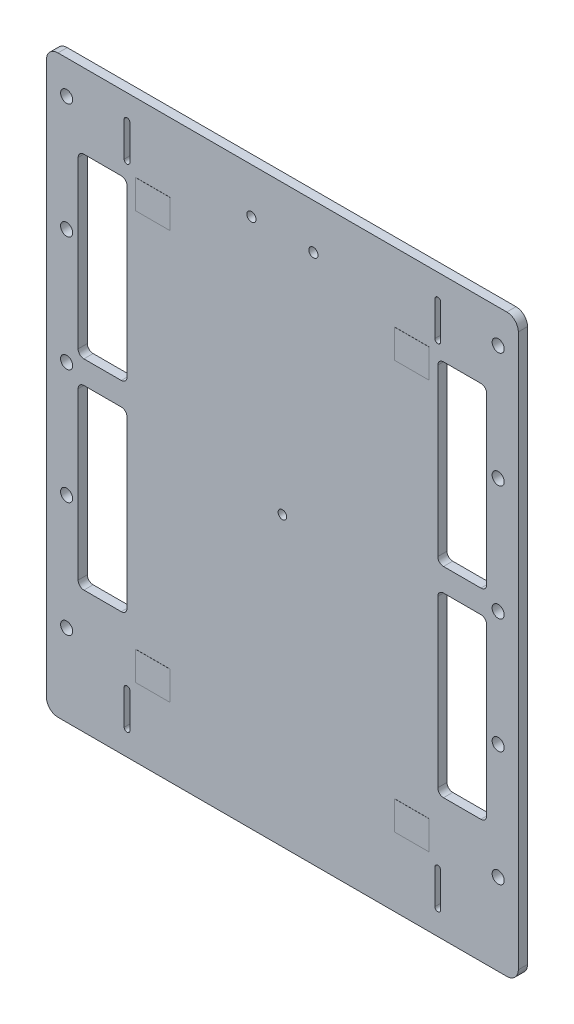
SolidWorks part; units mm, degrees
material "Oshpark board"
ref_plane "Front Plane" through (0, 0, 0) normal (0, 0, 1) x (1, 0, 0)
ref_plane "Top Plane" through (0, 0, 0) normal (0, 1, 0) x (1, 0, 0)
ref_plane "Right Plane" through (0, 0, 0) normal (1, 0, 0) x (0, 0, -1)
sketch "Sketch1" plane through (0, 0, 0) normal (0, 0, 1) x (1, 0, 0)
  line L1 (-39, -50) -> (39, -50)
  line L2 (-41, -48) -> (-41, 48)
  line L3 (-39, 50) -> (39, 50)
  line L4 (41, -48) -> (41, 48)
  line L5 (-41, -50) -> (41, 50) construction
  line L6 (-41, 50) -> (41, -50) construction
  arc A0 (-39, -50) -> (-41, -48) centre (-39, -48) cw
  arc A1 (39, -50) -> (41, -48) centre (39, -48) ccw
  arc A2 (39, 50) -> (41, 48) centre (39, 48) cw
  arc A3 (-41, 48) -> (-39, 50) centre (-39, 48) cw
  point P0 (0, 0)
  dimension "D3" = 2
  dimension "D1" = 100
  dimension "D2" = 82
extrude "Boss-Extrude1" add sketch "Sketch1" along normal blind 1.6
sketch "Sketch2" plane through (0, 0, 1.6) normal (0, 0, 1) x (1, 0, 0)
  line L0 (39, 50) -> (-39, 50) construction
  line L1 (-41, 48) -> (-41, -48) construction
  line L3 (-37.5, 44.2) -> (-37.5, 4.2) construction
  circle A0 centre (0, 0) radius 0.75
  circle A1 centre (-37.5, 44.2) radius 1.05
  circle A2 centre (37.5, 44.2) radius 1.05
  circle A3 centre (37.5, 4.2) radius 1.05
  circle A4 centre (37.5, -35.8) radius 1.05
  circle A5 centre (-37.5, 4.2) radius 1.05
  circle A6 centre (-37.5, -35.8) radius 1.05
  circle A7 centre (-5.38, 42.15) radius 0.8
  circle A8 centre (5.39, 42.15) radius 0.8
  dimension "D1" = 1.5
  dimension "D2" = 2.1
  dimension "D9" = 10.77
  dimension "D7" = 1.6
  dimension "D11" = 7.85
  dimension "D12" = 35.62
  dimension "D3" = 5.8
  dimension "D4" = 3.5
  dimension "D8" = 40
  dimension "D10" = 37.5
  dimension "D5" = 2
  dimension "D6" = 3
extrude "Cut-Extrude1" cut sketch "Sketch2" against normal through all
sketch "Sketch3" plane through (0, 0, 1.6) normal (0, 0, 1) x (1, 0, 0)
  line L0 (39, 50) -> (-39, 50) construction
  line L1 (-34.5, 37) -> (-28, 37)
  line L2 (-35.5, 36) -> (-35.5, 7.2)
  line L3 (-34.5, 6.2) -> (-28, 6.2)
  line L4 (-27, 36) -> (-27, 7.2)
  line L5 (-41, 48) -> (-41, -48) construction
  line L6 (28, 37) -> (34.5, 37)
  line L7 (27, 36) -> (27, 7.2)
  line L8 (35.5, 36) -> (35.5, 7.2)
  line L9 (28, 6.2) -> (34.5, 6.2)
  line L10 (28, 2.2) -> (34.5, 2.2)
  line L11 (27, 1.2) -> (27, -27.6)
  line L12 (35.5, 1.2) -> (35.5, -27.6)
  line L13 (28, -28.6) -> (34.5, -28.6)
  line L14 (-34.5, 2.2) -> (-28, 2.2)
  line L15 (-35.5, 1.2) -> (-35.5, -27.6)
  line L16 (-27, 1.2) -> (-27, -27.6)
  line L17 (-34.5, -28.6) -> (-28, -28.6)
  line L18 (-34.5, 37) -> (28, 37) construction
  line L19 (-39, -50) -> (39, -50) construction
  arc A0 (-35.5, 7.2) -> (-34.5, 6.2) centre (-34.5, 7.2) ccw
  arc A1 (-28, 6.2) -> (-27, 7.2) centre (-28, 7.2) ccw
  arc A2 (-28, 37) -> (-27, 36) centre (-28, 36) cw
  arc A3 (-34.5, 37) -> (-35.5, 36) centre (-34.5, 36) ccw
  arc A4 (28, 37) -> (27, 36) centre (28, 36) ccw
  arc A5 (34.5, 37) -> (35.5, 36) centre (34.5, 36) cw
  arc A6 (27, 7.2) -> (28, 6.2) centre (28, 7.2) ccw
  arc A7 (34.5, 6.2) -> (35.5, 7.2) centre (34.5, 7.2) ccw
  arc A8 (28, 2.2) -> (27, 1.2) centre (28, 1.2) ccw
  arc A9 (34.5, 2.2) -> (35.5, 1.2) centre (34.5, 1.2) cw
  arc A10 (27, -27.6) -> (28, -28.6) centre (28, -27.6) ccw
  arc A11 (34.5, -28.6) -> (35.5, -27.6) centre (34.5, -27.6) ccw
  arc A12 (-34.5, 2.2) -> (-35.5, 1.2) centre (-34.5, 1.2) ccw
  arc A13 (-28, 2.2) -> (-27, 1.2) centre (-28, 1.2) cw
  arc A14 (-35.5, -27.6) -> (-34.5, -28.6) centre (-34.5, -27.6) ccw
  arc A15 (-28, -28.6) -> (-27, -27.6) centre (-28, -27.6) ccw
  point P12 (-27, 6.2)
  point P15 (-27, 37)
  point P18 (-35.5, 37)
  dimension "D5" = 1
  dimension "D10" = 27
  dimension "D1" = 8.5
  dimension "D2" = 30.8
  dimension "D3" = 13
  dimension "D4" = 5.5
  dimension "D8" = 62.5
  dimension "D9" = 4
  dimension "D11" = 21.4
  dimension "D6" = 2
  dimension "D7" = 2
extrude "Cut-Extrude2" cut sketch "Sketch3" against normal through all
sketch "Sketch4" plane through (0, 0, 1.6) normal (0, 0, 1) x (1, 0, 0)
  line L0 (-27, 39.75) -> (-27, 45.75) construction
  line L1 (-27.5, 39.75) -> (-27.5, 45.75)
  line L2 (-26.5, 39.75) -> (-26.5, 45.75)
  line L3 (39, 50) -> (-39, 50) construction
  line L4 (-41, 48) -> (-41, -48) construction
  line L5 (27, 39.75) -> (27, 45.75) construction
  line L6 (26.5, 39.75) -> (26.5, 45.75)
  line L7 (27.5, 39.75) -> (27.5, 45.75)
  line L8 (27, -45.75) -> (27, -39.75) construction
  line L9 (26.5, -45.75) -> (26.5, -39.75)
  line L10 (27.5, -45.75) -> (27.5, -39.75)
  line L11 (-27, -45.75) -> (-27, -39.75) construction
  line L12 (-27.5, -45.75) -> (-27.5, -39.75)
  line L13 (-26.5, -45.75) -> (-26.5, -39.75)
  line L14 (-27, 39.75) -> (27, 39.75) construction
  line L15 (-39, -50) -> (39, -50) construction
  arc A0 (-27.5, 39.75) -> (-26.5, 39.75) centre (-27, 39.75) ccw
  arc A1 (-26.5, 45.75) -> (-27.5, 45.75) centre (-27, 45.75) ccw
  arc A2 (26.5, 39.75) -> (27.5, 39.75) centre (27, 39.75) ccw
  arc A3 (27.5, 45.75) -> (26.5, 45.75) centre (27, 45.75) ccw
  arc A4 (26.5, -45.75) -> (27.5, -45.75) centre (27, -45.75) ccw
  arc A5 (27.5, -39.75) -> (26.5, -39.75) centre (27, -39.75) ccw
  arc A6 (-27.5, -45.75) -> (-26.5, -45.75) centre (-27, -45.75) ccw
  arc A7 (-26.5, -39.75) -> (-27.5, -39.75) centre (-27, -39.75) ccw
  point P2 (-27, 42.75)
  point P16 (27, 42.75)
  point P23 (27, -42.75)
  point P30 (-27, -42.75)
  dimension "D1" = 4.25
  dimension "D2" = 13.5
  dimension "D3" = 1
  dimension "D4" = 6
  dimension "D7" = 54
  dimension "D8" = 14
  dimension "D9" = 4.25
  dimension "D10" = 4.25
  dimension "D5" = 2
  dimension "D6" = 2
extrude "Cut-Extrude3" cut sketch "Sketch4" against normal blind 1.6
sketch "Sketch5" plane through (0, 0, 1.6) normal (0, 0, 1) x (1, 0, 0)
  line L0 (-41, 48) -> (-41, -48) construction
  line L1 (-25.5, 38) -> (-19.5, 38)
  line L2 (-25.5, 38) -> (-25.5, 33)
  line L3 (-25.5, 33) -> (-19.5, 33)
  line L4 (-19.5, 38) -> (-19.5, 33)
  line L5 (39, 50) -> (-39, 50) construction
  line L6 (19.5, 38) -> (19.5, 33)
  line L7 (25.5, 38) -> (25.5, 33)
  line L8 (19.5, 33) -> (25.5, 33)
  line L9 (19.5, 38) -> (25.5, 38)
  line L10 (19.5, -33) -> (19.5, -38)
  line L11 (25.5, -33) -> (25.5, -38)
  line L12 (19.5, -38) -> (25.5, -38)
  line L13 (19.5, -33) -> (25.5, -33)
  line L14 (-25.5, -33) -> (-25.5, -38)
  line L15 (-19.5, -33) -> (-19.5, -38)
  line L16 (-25.5, -38) -> (-19.5, -38)
  line L17 (-25.5, -33) -> (-19.5, -33)
  line L18 (-25.5, 38) -> (19.5, 38) construction
  line L19 (-25.5, 38) -> (-25.5, -33) construction
  dimension "D1" = 5
  dimension "D2" = 6
  dimension "D3" = 15.5
  dimension "D4" = 12
  dimension "D7" = 45
  dimension "D8" = 71
  dimension "D5" = 2
  dimension "D6" = 2
extrude "Boss-Extrude2" add sketch "Sketch5" along normal blind 0.02
hole_wizard "M2 Clearance Hole1" positions "Sketch6" profile "Sketch7" hole size "M2" standard "ANSI Metric" end condition through all
sketch "Sketch6" plane through (0, 0, 0) normal (0, 0, -1) x (-1, 0, 0)
  line L0 (-37.5, 44.2) -> (-37.5, 4.2) construction
  line L2 (-37.5, 4.2) -> (37.5, 4.2) construction
  line L4 (0, 4.2) -> (0, 34.4116) construction
  point P0 (-37.5, 24.2)
  point P27 (-37.5, -15.8)
  point P32 (37.5, -15.8)
  point P33 (37.5, 24.2)
sketch "Sketch7" plane through (37.5, 24.2, 0) normal (1, 0, 0) x (0, 1, 0)
  line L0 (0, 0) -> (0, 1.62)
  line L1 (0, 1.62) -> (1.05, 1.62)
  line L2 (1.05, 1.62) -> (1.05, 0)
  line L5 (1.05, 0) -> (0, 0)
  line L11 (0, -6.35) -> (0, 107.95) construction
  dimension "Thru Hole Dia." = 2.1
  dimension "Thru Hole Depth" = 1.62
sketch "Sketch8" plane through (0, 0, 1.6) normal (0, 0, 1) x (1, 0, 0)
  line L0 (-15, -11.3) -> (-15, 19.7)
  line L1 (-15, -11.3) -> (-15, 19.7)
  line L2 (12, -14.3) -> (-12, -14.3)
  line L3 (12, -14.3) -> (-12, -14.3)
  line L4 (15, 19.7) -> (15, -11.3)
  line L5 (15, 19.7) -> (15, -11.3)
  line L6 (-12, 22.7) -> (12, 22.7)
  line L7 (-12, 22.7) -> (12, 22.7)
  line L8 (-32.5, 22.7) -> (-21, 22.7)
  line L9 (-32.5, 22.7) -> (-21, 22.7)
  line L10 (-35.5, 19.7) -> (-35.5, -11.3)
  line L11 (-35.5, 19.7) -> (-35.5, -11.3)
  line L12 (-21, -14.3) -> (-32.5, -14.3)
  line L13 (-21, -14.3) -> (-32.5, -14.3)
  line L14 (-18, 19.7) -> (-18, -11.3)
  line L15 (-18, 19.7) -> (-18, -11.3)
  line L16 (18, -11.3) -> (18, 19.7)
  line L17 (18, -11.3) -> (18, 19.7)
  line L18 (32.5, -14.3) -> (21, -14.3)
  line L19 (32.5, -14.3) -> (21, -14.3)
  line L20 (35.5, -11.3) -> (35.5, 19.7)
  line L21 (35.5, -11.3) -> (35.5, 19.7)
  line L22 (21, 22.7) -> (32.5, 22.7)
  line L23 (21, 22.7) -> (32.5, 22.7)
  line L24 (-15, -43) -> (-15, -20.3)
  line L25 (-15, -43) -> (-15, -20.3)
  line L26 (12, -46) -> (-12, -46)
  line L27 (12, -46) -> (-12, -46)
  line L28 (15, -20.3) -> (15, -43)
  line L29 (15, -20.3) -> (15, -43)
  line L30 (-12, -17.3) -> (12, -17.3)
  line L31 (-12, -17.3) -> (12, -17.3)
  line L32 (-35.5, -20.3) -> (-35.5, -43)
  line L33 (-35.5, -20.3) -> (-35.5, -43)
  line L34 (-32.5, -17.3) -> (-21, -17.3)
  line L35 (-32.5, -17.3) -> (-21, -17.3)
  line L36 (-18, -20.3) -> (-18, -43)
  line L37 (-18, -20.3) -> (-18, -43)
  line L38 (-21, -46) -> (-32.5, -46)
  line L39 (-21, -46) -> (-32.5, -46)
  line L40 (18, -43) -> (18, -20.3)
  line L41 (18, -43) -> (18, -20.3)
  line L42 (32.5, -46) -> (21, -46)
  line L43 (32.5, -46) -> (21, -46)
  line L44 (35.5, -43) -> (35.5, -20.3)
  line L45 (35.5, -43) -> (35.5, -20.3)
  line L46 (21, -17.3) -> (32.5, -17.3)
  line L47 (21, -17.3) -> (32.5, -17.3)
  line L48 (-15, 28.7) -> (-15, 42)
  line L49 (-15, 28.7) -> (-15, 42)
  line L50 (12, 25.7) -> (-12, 25.7)
  line L51 (12, 25.7) -> (-12, 25.7)
  line L52 (15, 42) -> (15, 28.7)
  line L53 (15, 42) -> (15, 28.7)
  line L54 (12, 45) -> (-12, 45)
  line L55 (12, 45) -> (-12, 45)
  line L56 (-35.5, 42) -> (-35.5, 28.7)
  line L57 (-35.5, 42) -> (-35.5, 28.7)
  line L58 (-21, 25.7) -> (-32.5, 25.7)
  line L59 (-21, 25.7) -> (-32.5, 25.7)
  line L60 (-18, 42) -> (-18, 28.7)
  line L61 (-18, 42) -> (-18, 28.7)
  line L62 (-21, 45) -> (-32.5, 45)
  line L63 (-21, 45) -> (-32.5, 45)
  line L64 (18, 28.7) -> (18, 42)
  line L65 (18, 28.7) -> (18, 42)
  line L66 (32.5, 25.7) -> (21, 25.7)
  line L67 (32.5, 25.7) -> (21, 25.7)
  line L68 (35.5, 28.7) -> (35.5, 42)
  line L69 (35.5, 28.7) -> (35.5, 42)
  line L70 (32.5, 45) -> (21, 45)
  line L71 (32.5, 45) -> (21, 45)
  line L72 (-32.5, -49) -> (-21, -49)
  line L73 (-32.5, -49) -> (-21, -49)
  line L74 (-12, -49) -> (12, -49)
  line L75 (-12, -49) -> (12, -49)
  line L76 (21, -49) -> (32.5, -49)
  line L77 (21, -49) -> (32.5, -49)
  line L78 (-39, -50) -> (39, -50) construction
  line L79 (41, -48) -> (41, 48) construction
  line L80 (39, 50) -> (-39, 50) construction
  line L81 (-41, 48) -> (-41, -48) construction
  line L82 (-39, -50) -> (39, -50)
  line L83 (41, -48) -> (41, 48)
  line L84 (39, 50) -> (-39, 50)
  line L85 (-41, 48) -> (-41, -48)
  arc A0 (-15, -11.3) -> (-12, -14.3) centre (-12, -11.3) ccw
  arc A1 (-15, -11.3) -> (-12, -14.3) centre (-12, -11.3) ccw
  arc A2 (12, -14.3) -> (15, -11.3) centre (12, -11.3) ccw
  arc A3 (12, -14.3) -> (15, -11.3) centre (12, -11.3) ccw
  arc A4 (15, 19.7) -> (12, 22.7) centre (12, 19.7) ccw
  arc A5 (15, 19.7) -> (12, 22.7) centre (12, 19.7) ccw
  arc A6 (-12, 22.7) -> (-15, 19.7) centre (-12, 19.7) ccw
  arc A7 (-12, 22.7) -> (-15, 19.7) centre (-12, 19.7) ccw
  arc A8 (-18, 19.7) -> (-21, 22.7) centre (-21, 19.7) ccw
  arc A9 (-18, 19.7) -> (-21, 22.7) centre (-21, 19.7) ccw
  arc A10 (-32.5, 22.7) -> (-35.5, 19.7) centre (-32.5, 19.7) ccw
  arc A11 (-32.5, 22.7) -> (-35.5, 19.7) centre (-32.5, 19.7) ccw
  arc A12 (-35.5, -11.3) -> (-32.5, -14.3) centre (-32.5, -11.3) ccw
  arc A13 (-35.5, -11.3) -> (-32.5, -14.3) centre (-32.5, -11.3) ccw
  arc A14 (-21, -14.3) -> (-18, -11.3) centre (-21, -11.3) ccw
  arc A15 (-21, -14.3) -> (-18, -11.3) centre (-21, -11.3) ccw
  arc A16 (18, -11.3) -> (21, -14.3) centre (21, -11.3) ccw
  arc A17 (18, -11.3) -> (21, -14.3) centre (21, -11.3) ccw
  arc A18 (32.5, -14.3) -> (35.5, -11.3) centre (32.5, -11.3) ccw
  arc A19 (32.5, -14.3) -> (35.5, -11.3) centre (32.5, -11.3) ccw
  arc A20 (35.5, 19.7) -> (32.5, 22.7) centre (32.5, 19.7) ccw
  arc A21 (35.5, 19.7) -> (32.5, 22.7) centre (32.5, 19.7) ccw
  arc A22 (21, 22.7) -> (18, 19.7) centre (21, 19.7) ccw
  arc A23 (21, 22.7) -> (18, 19.7) centre (21, 19.7) ccw
  arc A24 (-15, -43) -> (-12, -46) centre (-12, -43) ccw
  arc A25 (-15, -43) -> (-12, -46) centre (-12, -43) ccw
  arc A26 (12, -46) -> (15, -43) centre (12, -43) ccw
  arc A27 (12, -46) -> (15, -43) centre (12, -43) ccw
  arc A28 (15, -20.3) -> (12, -17.3) centre (12, -20.3) ccw
  arc A29 (15, -20.3) -> (12, -17.3) centre (12, -20.3) ccw
  arc A30 (-12, -17.3) -> (-15, -20.3) centre (-12, -20.3) ccw
  arc A31 (-12, -17.3) -> (-15, -20.3) centre (-12, -20.3) ccw
  arc A32 (-32.5, -17.3) -> (-35.5, -20.3) centre (-32.5, -20.3) ccw
  arc A33 (-32.5, -17.3) -> (-35.5, -20.3) centre (-32.5, -20.3) ccw
  arc A34 (-18, -20.3) -> (-21, -17.3) centre (-21, -20.3) ccw
  arc A35 (-18, -20.3) -> (-21, -17.3) centre (-21, -20.3) ccw
  arc A36 (-21, -46) -> (-18, -43) centre (-21, -43) ccw
  arc A37 (-21, -46) -> (-18, -43) centre (-21, -43) ccw
  arc A38 (-35.5, -43) -> (-32.5, -46) centre (-32.5, -43) ccw
  arc A39 (-35.5, -43) -> (-32.5, -46) centre (-32.5, -43) ccw
  arc A40 (18, -43) -> (21, -46) centre (21, -43) ccw
  arc A41 (18, -43) -> (21, -46) centre (21, -43) ccw
  arc A42 (32.5, -46) -> (35.5, -43) centre (32.5, -43) ccw
  arc A43 (32.5, -46) -> (35.5, -43) centre (32.5, -43) ccw
  arc A44 (35.5, -20.3) -> (32.5, -17.3) centre (32.5, -20.3) ccw
  arc A45 (35.5, -20.3) -> (32.5, -17.3) centre (32.5, -20.3) ccw
  arc A46 (21, -17.3) -> (18, -20.3) centre (21, -20.3) ccw
  arc A47 (21, -17.3) -> (18, -20.3) centre (21, -20.3) ccw
  arc A48 (-15, 28.7) -> (-12, 25.7) centre (-12, 28.7) ccw
  arc A49 (-15, 28.7) -> (-12, 25.7) centre (-12, 28.7) ccw
  arc A50 (12, 25.7) -> (15, 28.7) centre (12, 28.7) ccw
  arc A51 (12, 25.7) -> (15, 28.7) centre (12, 28.7) ccw
  arc A52 (15, 42) -> (12, 45) centre (12, 42) ccw
  arc A53 (15, 42) -> (12, 45) centre (12, 42) ccw
  arc A54 (-12, 45) -> (-15, 42) centre (-12, 42) ccw
  arc A55 (-12, 45) -> (-15, 42) centre (-12, 42) ccw
  arc A56 (-35.5, 28.7) -> (-32.5, 25.7) centre (-32.5, 28.7) ccw
  arc A57 (-35.5, 28.7) -> (-32.5, 25.7) centre (-32.5, 28.7) ccw
  arc A58 (-21, 25.7) -> (-18, 28.7) centre (-21, 28.7) ccw
  arc A59 (-21, 25.7) -> (-18, 28.7) centre (-21, 28.7) ccw
  arc A60 (-18, 42) -> (-21, 45) centre (-21, 42) ccw
  arc A61 (-18, 42) -> (-21, 45) centre (-21, 42) ccw
  arc A62 (-32.5, 45) -> (-35.5, 42) centre (-32.5, 42) ccw
  arc A63 (-32.5, 45) -> (-35.5, 42) centre (-32.5, 42) ccw
  arc A64 (18, 28.7) -> (21, 25.7) centre (21, 28.7) ccw
  arc A65 (18, 28.7) -> (21, 25.7) centre (21, 28.7) ccw
  arc A66 (32.5, 25.7) -> (35.5, 28.7) centre (32.5, 28.7) ccw
  arc A67 (32.5, 25.7) -> (35.5, 28.7) centre (32.5, 28.7) ccw
  arc A68 (35.5, 42) -> (32.5, 45) centre (32.5, 42) ccw
  arc A69 (35.5, 42) -> (32.5, 45) centre (32.5, 42) ccw
  arc A70 (21, 45) -> (18, 42) centre (21, 42) ccw
  arc A71 (21, 45) -> (18, 42) centre (21, 42) ccw
  arc A72 (-32.5, -49) -> (-35.5, -52) centre (-32.5, -52) ccw
  arc A73 (-32.5, -49) -> (-34.7361, -50) centre (-32.5, -52) ccw
  arc A74 (-18, -52) -> (-21, -49) centre (-21, -52) ccw
  arc A75 (-18.7639, -50) -> (-21, -49) centre (-21, -52) ccw
  arc A76 (-12, -49) -> (-15, -52) centre (-12, -52) ccw
  arc A77 (-12, -49) -> (-14.2361, -50) centre (-12, -52) ccw
  arc A78 (15, -52) -> (12, -49) centre (12, -52) ccw
  arc A79 (14.2361, -50) -> (12, -49) centre (12, -52) ccw
  arc A80 (21, -49) -> (18, -52) centre (21, -52) ccw
  arc A81 (21, -49) -> (18.7639, -50) centre (21, -52) ccw
  arc A82 (35.5, -52) -> (32.5, -49) centre (32.5, -52) ccw
  arc A83 (34.7361, -50) -> (32.5, -49) centre (32.5, -52) ccw
  arc A84 (-41, -48) -> (-39, -50) centre (-39, -48) ccw construction
  arc A85 (39, -50) -> (41, -48) centre (39, -48) ccw construction
  arc A86 (41, 48) -> (39, 50) centre (39, 48) ccw construction
  arc A87 (-39, 50) -> (-41, 48) centre (-39, 48) ccw construction
  arc A88 (-41, -48) -> (-39, -50) centre (-39, -48) ccw
  arc A89 (39, -50) -> (41, -48) centre (39, -48) ccw
  arc A90 (41, 48) -> (39, 50) centre (39, 48) ccw
  arc A91 (-39, 50) -> (-41, 48) centre (-39, 48) ccw
  point P144 (18.7639, -50)
